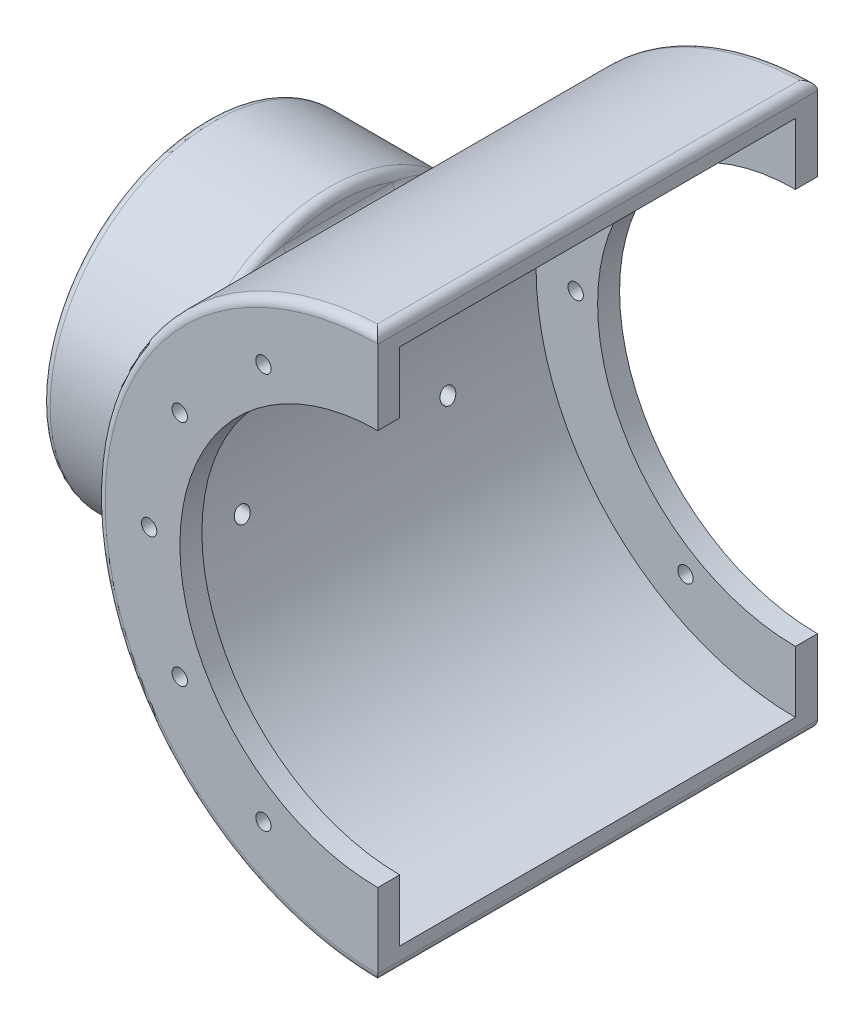
SolidWorks part; units mm, degrees
ref_plane "Front Plane" through (0, 0, 0) normal (0, 0, 1) x (1, 0, 0)
ref_plane "Top Plane" through (0, 0, 0) normal (0, 1, 0) x (1, 0, 0)
ref_plane "Right Plane" through (0, 0, 0) normal (1, 0, 0) x (0, 0, -1)
sketch "Sketch1" plane through (0, 0, 0) normal (0, 0, 1) x (1, 0, 0)
  line L0 (0, 59) -> (0, 45)
  line L1 (0, -45) -> (0, -59)
  arc A0 (0, 59) -> (0, -59) centre (0, 0) ccw
  arc A1 (0, 45) -> (0, -45) centre (0, 0) ccw
  dimension "D1" = 118
  dimension "D2" = 90
extrude "Boss-Extrude1" add sketch "Sketch1" along normal blind 90
shell "Shell2" thickness 5
sketch "Sketch5" plane through (0, 0, 95) normal (0, 0, 1) x (1, 0, 0)
  circle A0 centre (0, 0) radius 52 construction
  circle A1 centre (-52, 0) radius 1.75
  circle A2 centre (-45.0333, -26) radius 1.75
  circle A3 centre (-26, -45.0333) radius 1.75
  circle A11 centre (-26, 45.0333) radius 1.75
  circle A12 centre (-45.0333, 26) radius 1.75
  arc A13 (-1.7498, 51.9706) -> (1.7498, 51.9706) centre (0, 52) ccw
  arc A14 (27.5006, 44.1329) -> (24.4699, 45.8827) centre (26, 45.0333) ccw
  arc A15 (44.1329, 27.5006) -> (45.8827, 24.4699) centre (45.0333, 26) ccw
  arc A16 (51.9706, 1.7498) -> (51.9706, -1.7498) centre (52, 0) ccw
  arc A17 (-1.7498, -51.9706) -> (1.7498, -51.9706) centre (0, -52) ccw
  arc A18 (24.4699, -45.8827) -> (27.5006, -44.1329) centre (26, -45.0333) ccw
  arc A19 (45.8827, -24.4699) -> (44.1329, -27.5006) centre (45.0333, -26) ccw
  point P29 (0, 0)
  dimension "D1" = 104
  dimension "D2" = 3.5
  dimension "D3" = 12
extrude "Cut-Extrude1" cut sketch "Sketch5" against normal blind 47
ref_plane "Plane2" through (-59, 0, 0) normal (-1, 0, 0) x (0, 0, 1)
sketch "Sketch8" plane through (-59, 0, 0) normal (-1, 0, 0) x (0, 0, 1)
  line L0 (-5, 64) -> (95, -64) construction
  line L1 (95, -64) -> (-5, -64) construction
  circle A0 centre (45, 0) radius 37.5
  dimension "D1" = 75
extrude "Boss-Extrude2" add sketch "Sketch8" along normal blind 30
fillet "Fillet6" radius 2 11 edges at (-64, 0, 95) (-59, -37.5, 45) (-63.9487, -2.563, 82.4123) (-59, 37.5, 45) (-63.9487, 2.563, 7.5877) (-59, 24.7992, 45) (-59, -24.7992, 45) (-89, 0, 82.5) (-64, 0, -5) (0, 64, 45) (0, -64, 45)
sketch "Sketch9" plane through (-89, 0, 0) normal (-1, 0, 0) x (0, 0, 1)
  circle A0 centre (45, 0) radius 27 construction
  circle A1 centre (45, 27) radius 1.75
  circle A2 centre (68.3827, -13.5) radius 1.75
  circle A3 centre (21.6173, -13.5) radius 1.75
  point P12 (45, 0)
  dimension "D1" = 54
  dimension "D2" = 3.5
  dimension "D3" = 3
extrude "Cut-Extrude2" cut sketch "Sketch9" against normal blind 63
sketch "Sketch10" plane through (0, 0, -5) normal (0, 0, -1) x (-1, 0, 0)
  circle A0 centre (0, 0) radius 50 construction
  circle A1 centre (50, 0) radius 1.75
  circle A2 centre (25, -43.3013) radius 1.75
  circle A3 centre (-25, -43.3013) radius 1.75
  circle A4 centre (-50, 0) radius 1.75
  circle A5 centre (-25, 43.3013) radius 1.75
  circle A6 centre (25, 43.3013) radius 1.75
  point P18 (0, 0)
  dimension "D1" = 100
  dimension "D2" = 3.5
  dimension "D3" = 6
extrude "Cut-Extrude3" cut sketch "Sketch10" against normal blind 36
